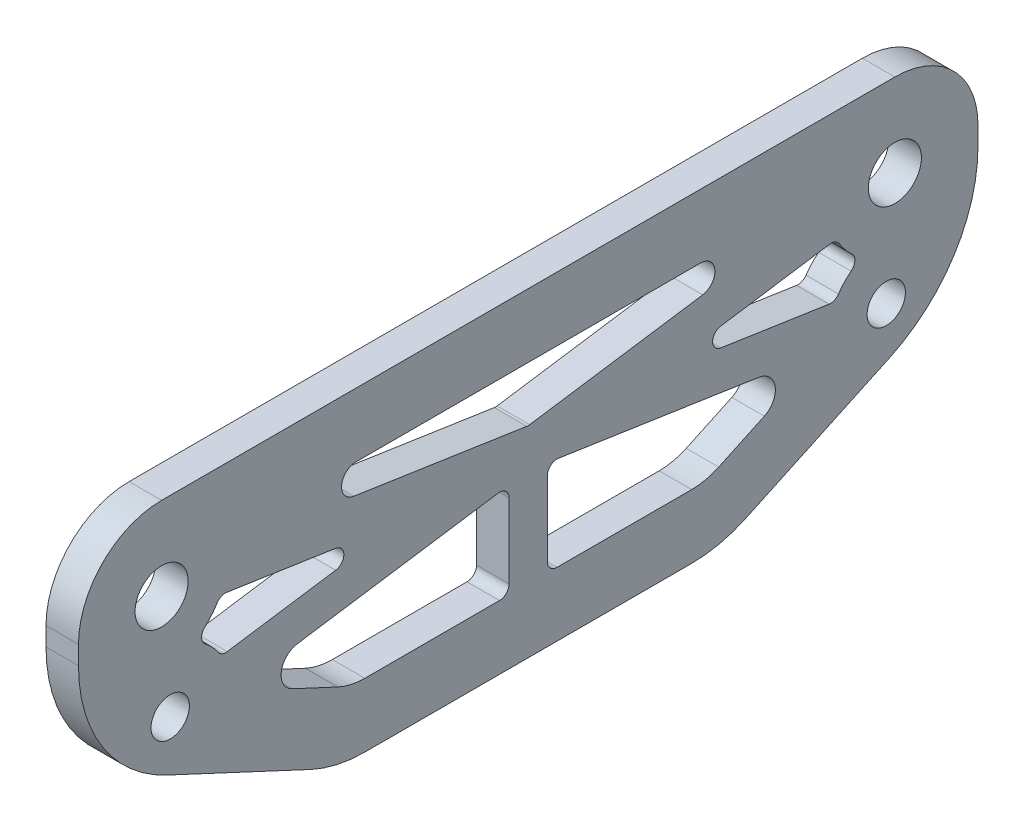
SolidWorks part; units mm, degrees
ref_plane "Front Plane" through (0, 0, 0) normal (0, 0, 1) x (1, 0, 0)
ref_plane "Top Plane" through (0, 0, 0) normal (0, 1, 0) x (1, 0, 0)
ref_plane "Right Plane" through (0, 0, 0) normal (1, 0, 0) x (0, 0, -1)
sketch "Sketch1" plane through (0, 0, 0) normal (1, 0, 0) x (0, 0, -1)
  line L0 (15, 12.5) -> (28.675, 12.5)
  line L1 (-15, -12.5) -> (15, -12.5)
  line L3 (-15, 12.5) -> (15, 12.5)
  line L5 (-15, -12.5) -> (15, 12.5) construction
  line L6 (-15, 12.5) -> (15, -12.5) construction
  line L8 (0, 12.5) -> (0, -12.5) construction
  line L10 (-15, 12.5) -> (-28.675, 12.5)
  line L11 (23.175, 136.0088) -> (23.175, -91.3912) construction
  line L13 (35.175, 6) -> (35.175, 4.5526)
  line L14 (28.2464, -6.3231) -> (15, -12.5)
  line L16 (-35.175, 6) -> (-35.175, 4.5526)
  line L17 (-28.2464, -6.3231) -> (-15, -12.5)
  arc A0 (28.675, 12.5) -> (35.175, 6) centre (28.675, 6) cw
  circle A1 centre (28.675, 6) radius 5.5 construction
  circle A2 centre (-28.675, 6) radius 5.5 construction
  arc A3 (-28.675, 12.5) -> (-35.175, 6) centre (-28.675, 6) ccw
  arc A4 (35.175, 4.5526) -> (28.2464, -6.3231) centre (23.175, 4.5526) cw
  circle A5 centre (28.675, 6) radius 2.075
  arc A6 (-35.175, 4.5526) -> (-28.2464, -6.3231) centre (-23.175, 4.5526) ccw
  circle A9 centre (-28.675, 6) radius 2.075
  circle A11 centre (28, -2.5) radius 1.5
  circle A12 centre (-28, -2.5) radius 1.5
  point P0 (0, 0)
  point P28 (0, 0)
  dimension "D1" = 11
  dimension "D2" = 1
  dimension "D3" = 4.15
  dimension "D4" = 3
  dimension "D6" = 25
  dimension "D8" = 12
  dimension "D5" = 25
  dimension "D7" = 30
  dimension "D9" = 28
  dimension "D10" = 2.5
extrude "Boss-Extrude1" add sketch "Sketch1" along normal blind 2.54
fillet "Fillet1" radius 10 2 edges at (1.27, -12.5, -15) (1.27, -12.5, 15)
sketch "Sketch2" plane through (0, 0, 0) normal (1, 0, 0) x (0, 0, -1)
  line L0 (-28.675, 6) -> (28, -2.5) construction
  line L10 (-28.675, -2.6012) -> (28.675, 6)
  line L11 (-28.675, 6) -> (28, -2.5)
  line L12 (-28.8975, 4.5166) -> (27.7775, -3.9834)
  line L13 (-28.4525, 7.4834) -> (28.2225, -1.0166)
  line L14 (-28.8975, 4.5166) -> (-28.4525, 7.4834)
  line L15 (27.7775, -3.9834) -> (28.2225, -1.0166)
  line L16 (-12.7831, -7.5) -> (12.7831, -7.5)
  line L17 (14.8961, -7.0315) -> (26.1333, -1.7916)
  line L18 (30.175, 4.5526) -> (30.175, 6)
  line L19 (28.675, 7.5) -> (-28.675, 7.5)
  line L20 (-30.175, 6) -> (-30.175, 4.5526)
  line L21 (-26.1333, -1.7916) -> (-14.8961, -7.0315)
  line L22 (-12.7831, -7.5) -> (12.7831, -7.5)
  line L23 (14.8961, -7.0315) -> (26.1333, -1.7916)
  line L24 (30.175, 4.5526) -> (30.175, 6)
  line L25 (28.675, 7.5) -> (-28.675, 7.5)
  line L26 (-30.175, 6) -> (-30.175, 4.5526)
  line L27 (-26.1333, -1.7916) -> (-14.8961, -7.0315)
  line L28 (-28.4525, -4.0846) -> (28.8975, 4.5166)
  line L29 (-28.8975, -1.1178) -> (28.4525, 7.4834)
  line L30 (-28.4525, -4.0846) -> (-28.8975, -1.1178)
  line L31 (28.8975, 4.5166) -> (28.4525, 7.4834)
  line L32 (0, -7.5) -> (0, 7.5) construction
  line L33 (0, 1.6994) -> (0, -7.5)
  line L34 (-1.5, 1.6994) -> (-1.5, -7.5)
  line L35 (1.5, 1.6994) -> (1.5, -7.5)
  line L36 (-1.5, 1.6994) -> (1.5, 1.6994)
  line L37 (-1.5, -7.5) -> (1.5, -7.5)
  arc A0 (-18.0527, -2.5249) -> (-18.4641, -5.3678) centre (-17.8302, -4.0083) ccw
  arc A1 (18.0527, -2.5249) -> (18.4641, -5.3678) centre (17.8302, -4.0083) cw
  circle A2 centre (-28, -2.5) radius 4.5
  circle A3 centre (-28, -2.5) radius 4.5
  circle A5 centre (28, -2.5) radius 4.5
  circle A6 centre (28, -2.5) radius 4.5
  circle A11 centre (-28.675, 6) radius 5.075
  arc A12 (12.7831, -7.5) -> (14.8961, -7.0315) centre (12.7831, -2.5) ccw
  arc A13 (26.1333, -1.7916) -> (30.175, 4.5526) centre (23.175, 4.5526) ccw
  arc A14 (30.175, 6) -> (28.675, 7.5) centre (28.675, 6) ccw
  arc A15 (-28.675, 7.5) -> (-30.175, 6) centre (-28.675, 6) ccw
  arc A16 (-30.175, 4.5526) -> (-26.1333, -1.7916) centre (-23.175, 4.5526) ccw
  arc A17 (-14.8961, -7.0315) -> (-12.7831, -7.5) centre (-12.7831, -2.5) ccw
  arc A18 (12.7831, -7.5) -> (14.8961, -7.0315) centre (12.7831, -2.5) ccw
  arc A19 (26.1333, -1.7916) -> (30.175, 4.5526) centre (23.175, 4.5526) ccw
  arc A20 (30.175, 6) -> (28.675, 7.5) centre (28.675, 6) ccw
  arc A21 (-28.675, 7.5) -> (-30.175, 6) centre (-28.675, 6) ccw
  arc A22 (-30.175, 4.5526) -> (-26.1333, -1.7916) centre (-23.175, 4.5526) ccw
  arc A23 (-14.8961, -7.0315) -> (-12.7831, -7.5) centre (-12.7831, -2.5) ccw
  circle A24 centre (-28.675, 6) radius 5.075
  circle A26 centre (28.675, 6) radius 5.075
  circle A27 centre (28.675, 6) radius 5.075
  arc A32 (13.477, 7.5) -> (13.6439, 5.2624) centre (13.477, 6.375) cw
  arc A33 (-13.477, 7.5) -> (-13.6439, 5.2624) centre (-13.477, 6.375) ccw
  dimension "D11" = 3
  dimension "D12" = 1.125
  dimension "D2" = 1.5
  dimension "D1" = 5
  dimension "D3" = 3
  dimension "D4" = 3
  dimension "D6" = 1.5
  dimension "D7" = 1.5
  dimension "D8" = 1.5
  dimension "D9" = 1.5
  dimension "D13" = 1.5
  dimension "D14" = 1.5
  dimension "D15" = 3
extrude "Cut-Extrude2" cut sketch "Sketch2" along normal through all contours A24 A3 L29 L12 | A27 L28 L13 A6 | L25 A33 L13 L29 A32 | A1 L12 L35 L22 | L28 A0 L22 L34 region at (0, 1.7005, 19.9688) region at (0, -4.2389, 9.1911) region at (0, 5.8357, 0) region at (0, -4.2389, -9.1911) region at (0, 1.7005, -19.9688)
fillet "Fillet2" radius 0.75 13 edges at (1.27, -7.5, -1.5) (1.27, 3.7975, -24.1028) (1.27, 1.6994, -10.1133) (1.27, 3.7975, 24.1028) (1.27, 3.2162, 0) (1.27, -0.0424, -1.5) (1.27, -7.5, 1.5) (1.27, -0.0424, 1.5) (1.27, 1.6994, 10.1133) (1.27, -0.3873, -24.0268) (1.27, 1.6002, -26.1457) (1.27, -0.3873, 24.0268) (1.27, 1.6002, 26.1457)
